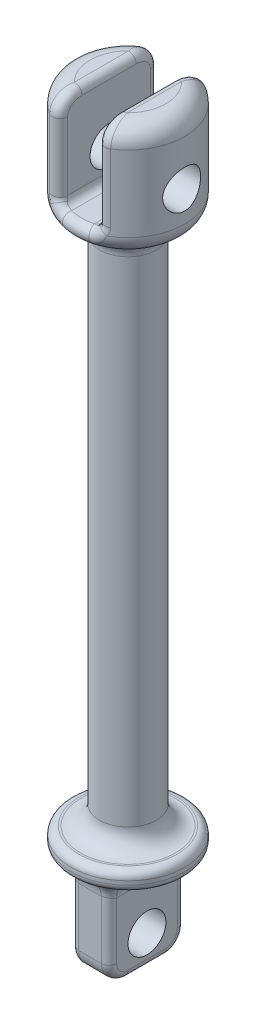
SolidWorks part; units mm, degrees
ref_plane "Front Plane" through (0, 0, 0) normal (0, 0, 1) x (1, 0, 0)
ref_plane "Top Plane" through (0, 0, 0) normal (0, 1, 0) x (1, 0, 0)
ref_plane "Right Plane" through (0, 0, 0) normal (1, 0, 0) x (0, 0, -1)
sketch "Sketch1" plane through (0, 0, 0) normal (0, 1, 0) x (1, 0, 0)
  circle A0 centre (0, 0) radius 15
  dimension "D1" = 30
extrude "Boss-Extrude1" add sketch "Sketch1" along normal mid plane 30
sketch "Sketch2" plane through (0, 15, 0) normal (0, 1, 0) x (1, 0, 0)
  line L0 (0, 15) -> (0, -15) construction
  line L1 (-5, 20) -> (5, 20)
  line L2 (-5, 20) -> (-5, -20)
  line L3 (-5, -20) -> (5, -20)
  line L4 (5, 20) -> (5, -20)
  line L5 (-15, 0) -> (15, 0) construction
  circle A0 centre (0, 0) radius 15 construction
  dimension "D1" = 10
  dimension "D2" = 40
extrude "Cut-Extrude2" cut sketch "Sketch2" against normal blind 25
sketch "Sketch3" plane through (-5, 0, 0) normal (1, 0, 0) x (0, 0, -1)
  line L0 (-14.1421, -2) -> (14.1421, -2) construction
  line L1 (0, -2) -> (0, 15) construction
  line L4 (14.1421, 15) -> (-14.1421, 15)
  line L5 (-14.1421, 15) -> (-14.1421, -10)
  line L6 (-14.1421, -10) -> (14.1421, -10)
  line L7 (14.1421, -10) -> (14.1421, 15)
  line L8 (14.1421, 15) -> (-14.1421, 15) construction
  line L9 (-14.1421, 15) -> (-14.1421, -10) construction
  line L10 (-14.1421, -10) -> (14.1421, -10) construction
  line L11 (14.1421, -10) -> (14.1421, 15) construction
  circle A0 centre (0, -2) radius 5
  dimension "D3" = 10
  dimension "D2" = 17
  dimension "D1" = 0
extrude "Cut-Extrude3" cut sketch "Sketch3" against normal through all both and the other way through all
fillet "Fillet3" radius 2 2 edges at (-5, -10, 0) (5, -10, 0)
sketch "Sketch4" plane through (0, -15, 0) normal (0, -1, 0) x (1, 0, 0)
  circle A0 centre (0, 0) radius 7.5
  dimension "D1" = 15
extrude "Boss-Extrude2" add sketch "Sketch4" along normal blind 140
fillet "Fillet6" radius 5 1 edges at (0, -15, 15)
fillet "Fillet7" radius 5 1 edges at (0, -15, -7.5)
sketch "Sketch6" plane through (0, -155, 0) normal (0, -1, 0) x (1, 0, 0)
  circle A0 centre (0, 0) radius 15
extrude "Boss-Extrude3" add sketch "Sketch6" along normal blind 5
fillet "Fillet9" radius 5 1 edges at (0, -155, -7.5)
fillet "Fillet11" radius 2 2 edges at (0, -160, -15) (0, -155, -15)
fillet "Fillet12" radius 5 1 edges at (-15, 15, 0)
fillet "Fillet13" radius 5 1 edges at (15, 15, 0)
fillet "Fillet15" radius 2 16 edges at (-5, 15, 0) (-5, 13.6688, 12.4291) (-5, 12.9768, -13.0952) (-5, 1, 14.1421) (-5, 1, -14.1421) (-4.2722, -9.5432, 14.3787) (-4.599, -9.2014, -14.2776) (0, -10, 15) (4.599, -9.2014, 14.2776) (5, 1, 14.1421) (5, 12.9768, 13.0952) (5, 15, 0) (0, -10, -15) (4.2722, -9.5432, -14.3787) (5, 1, -14.1421) (5, 13.6688, -12.4291)
sketch "Sketch9" plane through (0, 0, 0) normal (1, 0, 0) x (0, 0, -1)
  line L0 (-13, -160) -> (13, -160) construction
  line L1 (-10, -160) -> (10, -160)
  line L2 (-10, -160) -> (-10, -180)
  line L3 (-5, -185) -> (5, -185)
  line L4 (10, -160) -> (10, -180)
  line L5 (-13, -160) -> (13, -160) construction
  circle A0 centre (0, -177) radius 5
  arc A1 (5, -185) -> (10, -180) centre (5, -180) ccw
  arc A2 (-10, -180) -> (-5, -185) centre (-5, -180) ccw
  point P6 (0, -160)
  point P7 (0, -160)
  point P10 (0, 0)
  point P11 (0, 0)
  point P14 (10, -185)
  point P17 (-10, -185)
  dimension "D3" = 10
  dimension "D5" = 5
  dimension "D1" = 25
  dimension "D2" = 20
  dimension "D4" = 17
extrude "Boss-Extrude5" add sketch "Sketch9" along normal mid plane 10
fillet "Fillet17" radius 2 5 edges at (5, -170, 10) (5, -183.5355, 8.5355) (5, -185, 0) (5, -183.5355, -8.5355) (5, -170, -10)
fillet "Fillet18" radius 2 5 edges at (-5, -170, 10) (-5, -183.5355, 8.5355) (-5, -170, -10) (-5, -183.5355, -8.5355) (-5, -185, 0)
fillet "Fillet19" radius 5 8 edges at (-4.4142, -160, -9.4142) (0, -160, -10) (4.4142, -160, -9.4142) (5, -160, 0) (4.4142, -160, 9.4142) (0, -160, 10) (-4.4142, -160, 9.4142) (-5, -160, 0)
